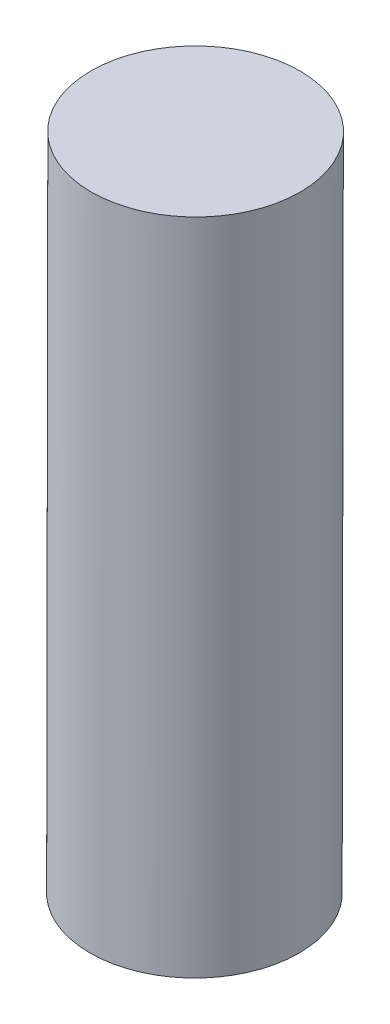
SolidWorks part; units mm, degrees
ref_plane "X-Y Datum" through (0, 0, 0) normal (0, 0, 1) x (1, 0, 0)
ref_plane "X-Z Datum" through (0, 0, 0) normal (0, 1, 0) x (1, 0, 0)
ref_plane "Y-Z Datum" through (0, 0, 0) normal (1, 0, 0) x (0, 0, -1)
sketch3d "3DSketch1"
  line L0 (-266.5648, 162.8505, 163.3218) -> (-266.5651, 163.3505, 163.3218) construction
  line L1 (-266.6171, 133.2199, 163.3218) -> (-266.5648, 162.8505, 163.3218)
  arc A0 (-266.6171, 133.2199, 166.8218) -> (-266.6171, 133.2199, 159.8218) centre (-266.6171, 133.2199, 163.3218) ccw construction
  point P0 (-266.6171, 133.2199, 163.3218)
  point P1 (-266.5648, 162.8505, 163.3218)
  point P5 (-266.6195, 136.7199, 163.3218)
sweep "Sweep1" add path "3DSketch1" circular profile diameter 9.398 parameters "D3"=9.398
